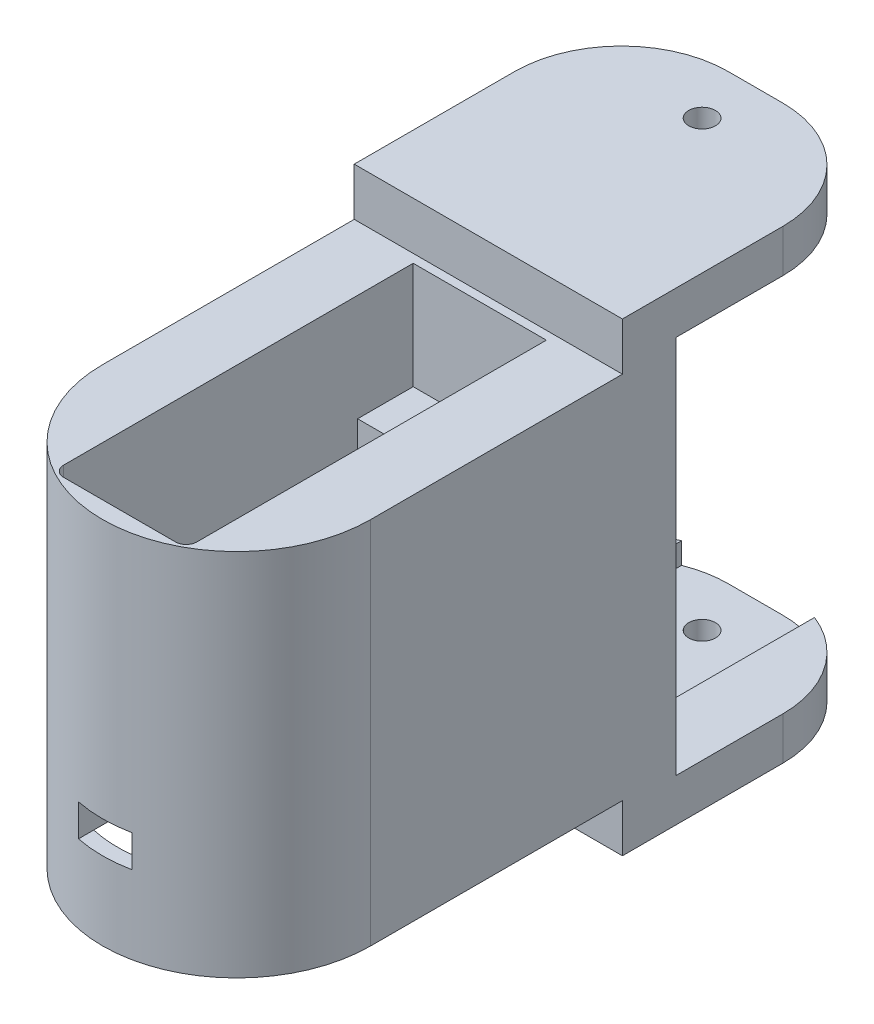
SolidWorks part; units mm, degrees
ref_plane "Front Plane" through (0, 0, 0) normal (0, 0, 1) x (1, 0, 0)
ref_plane "Top Plane" through (0, 0, 0) normal (0, 1, 0) x (1, 0, 0)
ref_plane "Right Plane" through (0, 0, 0) normal (1, 0, 0) x (0, 0, -1)
sketch "Sketch4" plane through (0, 0, 0) normal (0, 0, 1) x (1, 0, 0)
  line L1 (-6.23, -9.975) -> (6.23, -9.975)
  line L2 (-6.23, -9.975) -> (-6.23, 7.275)
  line L3 (-6.23, 7.275) -> (6.23, 7.275)
  line L4 (6.23, -9.975) -> (6.23, 7.275)
  point P4 (0, 7.275)
  dimension "D1" = 12.46
  dimension "D2" = 17.25
  dimension "D3" = 9.975
extrude "Boss-Extrude3" add sketch "Sketch4" along normal blind 6
sketch "Sketch8" plane through (0, -9.975, 0) normal (0, -1, 0) x (-1, 0, 0)
  circle A0 centre (0, -23.55) radius 12.5468
  circle A1 centre (0, -23.55) radius 11.15
  dimension "D1" = 22.3
  dimension "D2" = 23.55
extrude "Boss-Extrude6" add sketch "Sketch8" along normal blind 7.3 and the other way up to surface (17.25 mm away) other way up to face at (0, 7.275, 3)
sketch "Sketch5" plane through (0, 7.275, 0) normal (0, 1, 0) x (1, 0, 0)
  line L8 (12.5468, -23.55) -> (12.5468, 0)
  line L9 (12.5468, 0) -> (6.23, 0)
  line L10 (-12.5468, -23.55) -> (-12.5468, 0)
  line L11 (-12.5468, 0) -> (-6.23, 0)
  line L12 (-6.23, 0) -> (-6.23, -29.7)
  line L14 (6.23, -29.7) -> (6.23, 0)
  line L15 (-6.23, -29.7) -> (6.23, -29.7)
  line L16 (6.23, -6) -> (-6.23, -6) construction
  circle A0 centre (0, -23.55) radius 12.5468 construction
  arc A1 (-12.5468, -23.55) -> (12.5468, -23.55) centre (0, -23.55) ccw
  dimension "D1" = 23.7
  dimension "D2" = 23.55
extrude "Boss-Extrude4" add sketch "Sketch5" against normal up to surface (17.25 mm away) up to face at (0, -9.975, 3)
sketch "Sketch6" plane through (0, 7.275, 0) normal (0, 1, 0) x (1, 0, 0)
  line L0 (6.23, -6) -> (-6.23, -6) construction
  line L3 (6.23, -29.7) -> (-6.23, -29.7) construction
  circle A0 centre (0, -3.5) radius 2
  circle A1 centre (0, -32.2) radius 2
  dimension "D1" = 4
  dimension "D3" = 4
  dimension "D2" = 2.5
  dimension "D4" = 2.5
extrude "Cut-Extrude1" cut sketch "Sketch6" against normal blind 5
chamfer "Chamfer1" distance 0.5 angle 60 2 edges at (0, 7.275, 5.5) (0, 7.275, 34.2) first distance on face at (0, 7.275, 5.5)
sketch "Sketch10" plane through (0, 7.275, 0) normal (0, 1, 0) x (1, 0, 0)
  line L1 (-6.23, -6) -> (6.23, -6)
  line L2 (-6.23, -6) -> (-6.23, -29.7)
  line L3 (-6.23, -29.7) -> (6.23, -29.7)
  line L4 (6.23, -6) -> (6.23, -29.7)
extrude "Cut-Extrude3" cut sketch "Sketch10" against normal up to surface (17.25 mm away) up to face at (0, -9.975, 27.1007)
ref_plane "Plane1" through (0, 0, 36.0968) normal (0, 0, 1) x (1, 0, 0)
sketch "Sketch11" plane through (0, 0, 36.0968) normal (0, 0, 1) x (1, 0, 0)
  line L0 (-11.15, -9.975) -> (11.15, -9.975) construction
  line L1 (-2.5, -6.975) -> (2.5, -6.975)
  line L2 (-2.5, -6.975) -> (-2.5, -9.975)
  line L3 (-2.5, -9.975) -> (2.5, -9.975)
  line L4 (2.5, -6.975) -> (2.5, -9.975)
  point P4 (0, -6.975)
  dimension "D1" = 0
  dimension "D2" = 5
  dimension "D3" = 3
extrude "Cut-Extrude4" cut sketch "Sketch11" against normal up to next
sketch "Sketch13" plane through (0, -17.275, 0) normal (0, -1, 0) x (1, 0, 0)
  line L0 (-12.5468, 23.55) -> (-12.5468, 0)
  line L1 (-12.5468, 0) -> (12.5468, 0)
  line L2 (12.5468, 0) -> (12.5468, 23.55)
  arc A0 (-12.5468, 23.55) -> (12.5468, 23.55) centre (0, 23.55) ccw
  point P3 (0, 0)
extrude "Boss-Extrude7" add sketch "Sketch13" against normal up to surface (7.3 mm away) up to face at (-6.0145, -9.975, 27.3356)
sketch "Sketch15" plane through (0, 7.275, 0) normal (0, 1, 0) x (1, 0, 0)
  line L0 (-12.5468, 0) -> (12.5468, 0)
  line L1 (12.5468, 0) -> (12.5468, -23.55)
  line L2 (-12.5468, 0) -> (-12.5468, -23.55)
  line L3 (6.23, -6) -> (6.23, -29.7) construction
  line L4 (-6.23, -0.8) -> (6.23, -0.8)
  line L5 (-6.23, -0.8) -> (-6.23, -33.5)
  line L6 (-5.23, -34.5) -> (5.23, -34.5)
  line L7 (6.23, -0.8) -> (6.23, -33.5)
  arc A0 (-12.5468, -23.55) -> (12.5468, -23.55) centre (0, -23.55) ccw
  circle A1 centre (0, -3.5) radius 2 construction
  arc A2 (5.23, -34.5) -> (6.23, -33.5) centre (5.23, -33.5) ccw
  arc A3 (-6.23, -33.5) -> (-5.23, -34.5) centre (-5.23, -33.5) ccw
  point P15 (0, -0.8)
  dimension "D1" = 0.8
  dimension "D3" = 1
  dimension "D2" = 2.7
  dimension "D4" = 0
  dimension "D5" = 34.5
extrude "Boss-Extrude9" add sketch "Sketch15" along normal blind 10
sketch "Sketch17" plane through (-12.5468, 4.7282, 0) normal (1, 0, 0) x (0, -1, 0)
  line L0 (26.4782, 25) -> (26.4782, 0)
  line L1 (26.4782, 0) -> (-17.0218, 0)
  line L2 (-17.0218, 0) -> (-17.0218, 25)
  line L3 (-17.0218, 25) -> (-13.0218, 25)
  line L4 (-13.0218, 25) -> (-13.0218, 5)
  line L5 (-13.0218, 5) -> (22.4782, 5)
  line L6 (22.4782, 5) -> (22.4782, 25)
  line L7 (22.4782, 25) -> (26.4782, 25)
  point P2 (4.7282, 5)
  point P10 (4.7282, 0)
  dimension "D1" = 4
  dimension "D2" = 35.5
  dimension "D3" = 0
  dimension "D4" = 25
  dimension "D5" = 5
extrude "Boss-Extrude10" add sketch "Sketch17" along normal up to surface (25.0936 mm away) up to face at (12.5468, 0, 11.775)
sketch "Sketch18" plane through (0, -17.75, 0) normal (0, 1, 0) x (0, 0, 1)
  line L0 (-25, -12.5468) -> (-25, 12.5468) construction
  line L1 (-25, 6.2191) -> (-5, 6.2191)
  line L2 (-25, 6.2191) -> (-25, -6.2191)
  line L3 (-25, -6.2191) -> (-5, -6.2191)
  line L4 (-5, 6.2191) -> (-5, -6.2191)
  line L5 (-5, -12.5468) -> (-5, 12.5468) construction
  point P6 (-25, 0)
  point P7 (-25, 0)
  dimension "D1" = 0
extrude "Cut-Extrude5" cut sketch "Sketch18" against normal blind 2
sketch "Sketch19" plane through (0, -19.75, 0) normal (0, 1, 0) x (0, 0, 1)
  line L0 (-25, -12.5468) -> (-25, 12.5468) construction
  circle A0 centre (-20, 0) radius 1.25
  dimension "D1" = 2.5
  dimension "D2" = 5
extrude "Cut-Extrude6" cut sketch "Sketch19" against normal through all both and the other way through all
fillet "Fillet1" radius 10 4 edges at (12.5468, -19.75, -25) (-12.5468, -19.75, -25) (-12.5468, 19.75, -25) (12.5468, 19.75, -25)
ref_plane "Plane2" through (0, 0, 0) normal (1, 0, 0) x (0, 0, -1)
ref_plane "Plane3" through (0, 0, 0) normal (0, -1, 0) x (-1, 0, 0)
